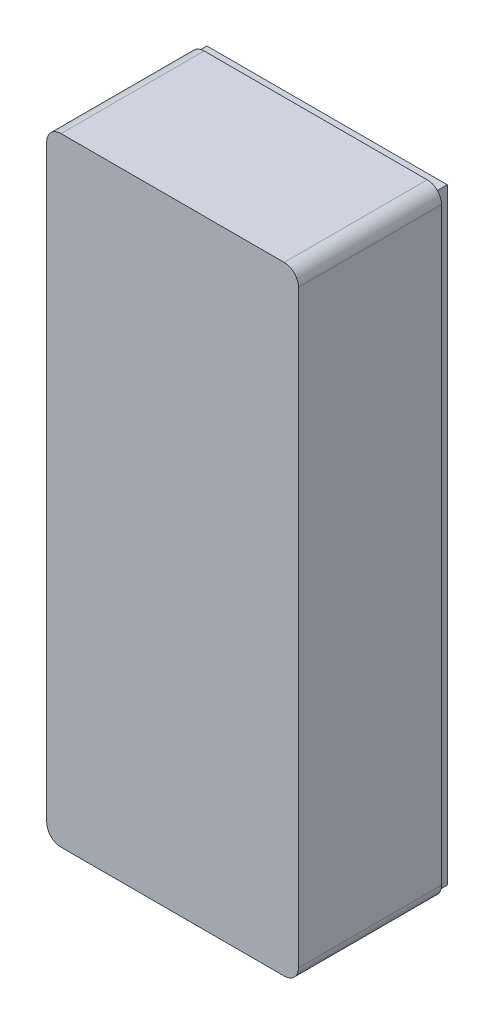
SolidWorks part; units mm, degrees
ref_plane "Přední rovina" through (0, 0, 0) normal (0, 0, 1) x (1, 0, 0)
ref_plane "Horní rovina" through (0, 0, 0) normal (0, 1, 0) x (1, 0, 0)
ref_plane "Pravá rovina" through (0, 0, 0) normal (1, 0, 0) x (0, 0, -1)
sketch "Skica1" plane through (0, 0, 0) normal (0, 0, 1) x (1, 0, 0)
  line L1 (0, 0) -> (44, 0)
  line L2 (0, 0) -> (0, 108)
  line L3 (0, 108) -> (44, 108)
  line L4 (44, 0) -> (44, 108)
  line L5 (2, 2) -> (42, 2)
  line L6 (2, 2) -> (2, 106)
  line L7 (2, 106) -> (42, 106)
  line L8 (42, 2) -> (42, 106)
  point P9 (22, 0)
  dimension "D1" = 108
  dimension "D2" = 44
  dimension "D3" = 2
  dimension "D4" = 2
  dimension "D5" = 2
  dimension "D6" = 2
extrude "Přidat vysunutím1" add sketch "Skica1" along normal blind 25
sketch "Skica2" plane through (0, 0, 25) normal (0, 0, 1) x (1, 0, 0)
  line L1 (0, 108) -> (44, 108)
  line L2 (0, 108) -> (0, 0)
  line L3 (0, 0) -> (44, 0)
  line L4 (44, 108) -> (44, 0)
extrude "Přidat vysunutím2" add sketch "Skica2" along normal blind 2
fillet "Zaoblit1" radius 2.5 4 edges at (0, 108, 13.5) (0, 0, 13.5) (44, 0, 13.5) (44, 108, 13.5)
sketch "Skica3" plane through (0, 0, 0) normal (0, 0, -1) x (-1, 0, 0)
  line L6 (-44, 2.5) -> (-44, 105.5) construction
  line L7 (-43, 107) -> (-1, 107)
  line L8 (-43, 107) -> (-43, 1)
  line L9 (-43, 1) -> (-1, 1)
  line L10 (-1, 107) -> (-1, 1)
  line L11 (0, 105.5) -> (0, 2.5) construction
  line L12 (-2.5, 0) -> (-41.5, 0) construction
  line L13 (-41.5, 108) -> (-2.5, 108) construction
  line L17 (0, 0) -> (-44, 0)
  line L18 (0, 0) -> (0, 108)
  line L19 (0, 108) -> (-44, 108)
  line L20 (-44, 0) -> (-44, 108)
  dimension "D1" = 1
  dimension "D2" = 1
  dimension "D3" = 1
  dimension "D4" = 1
extrude "Odebrat vysunutím1" cut sketch "Skica3" against normal blind 2
sketch "Skica4" plane through (0, 0, 25) normal (0, 0, -1) x (-1, 0, 0)
  line L0 (-42, 2) -> (-42, 10)
  line L9 (-42, 2) -> (-42, 106) construction
  line L10 (-42, 2) -> (-34, 2)
  line L11 (-2, 2) -> (-42, 2) construction
  line L12 (-2, 2) -> (-10, 2)
  line L13 (-2, 2) -> (-2, 10)
  line L14 (-2, 106) -> (-2, 2) construction
  line L15 (-2, 80) -> (-2, 76)
  line L16 (-2, 106) -> (-2, 2) construction
  line L17 (-2, 76) -> (-5, 76)
  line L18 (-2, 80) -> (-2, 84)
  line L19 (-2, 84) -> (-5, 84)
  line L20 (-42, 84) -> (-39, 84)
  line L21 (-42, 2) -> (-42, 106) construction
  line L22 (-42, 84) -> (-42, 76)
  line L23 (-42, 76) -> (-39, 76)
  circle A0 centre (-39, 5) radius 1.5
  circle A1 centre (-5, 5) radius 1.5
  circle A2 centre (-39, 80) radius 1.5
  circle A3 centre (-5, 80) radius 1.5
  arc A4 (-34, 2) -> (-42, 10) centre (-42, 2) ccw
  arc A5 (-2, 10) -> (-10, 2) centre (-2, 2) ccw
  arc A6 (-5, 84) -> (-5, 76) centre (-5, 80) ccw
  arc A7 (-39, 84) -> (-39, 76) centre (-39, 80) cw
  dimension "D2" = 3
  dimension "D5" = 3
  dimension "D4" = 3
  dimension "D6" = 3
  dimension "D7" = 8
  dimension "D9" = 8
  dimension "D10" = 4
  dimension "D1" = 75
  dimension "D3" = 75
  dimension "D8" = 8
  dimension "D11" = 4
extrude "Přidat vysunutím3" add sketch "Skica4" along normal blind 22
sketch "Skica6" plane through (0, 0, 0) normal (0, -1, 0) x (1, 0, 0)
  line L3 (22, 10.4) -> (15.25, 10.4)
  line L4 (15.25, 10.4) -> (15.25, 5)
  line L5 (15.25, 5) -> (28.75, 5)
  line L6 (28.75, 5) -> (28.75, 10.4)
  line L7 (28.75, 10.4) -> (22, 10.4)
  dimension "D3" = 6.75
  dimension "D4" = 13.5
extrude "Odebrat vysunutím2" cut sketch "Skica6" against normal blind 10
sketch "Skica7" plane through (0, 0, 25) normal (0, 0, -1) x (-1, 0, 0)
  line L0 (-42, 16) -> (-2, 16)
  line L1 (-42, 10) -> (-42, 76) construction
  line L2 (-2, 76) -> (-2, 10) construction
  line L3 (-42, 76) -> (-39, 76) construction
  line L4 (-42, 16) -> (-42, 14)
  line L5 (-42, 14) -> (-2, 14)
  line L6 (-2, 14) -> (-2, 16)
  line L7 (-42, 63.683) -> (-37, 63.683)
  line L8 (-37, 63.683) -> (-37, 65.683)
  line L9 (-37, 65.683) -> (-42, 65.683)
  line L10 (-42, 2) -> (-42, 106) construction
  line L11 (-42, 65.683) -> (-42, 63.683)
  dimension "D1" = 60
  dimension "D2" = 2
  dimension "D3" = 5
  dimension "D4" = 2
extrude "Přidat vysunutím4" add sketch "Skica7" along normal blind 10
